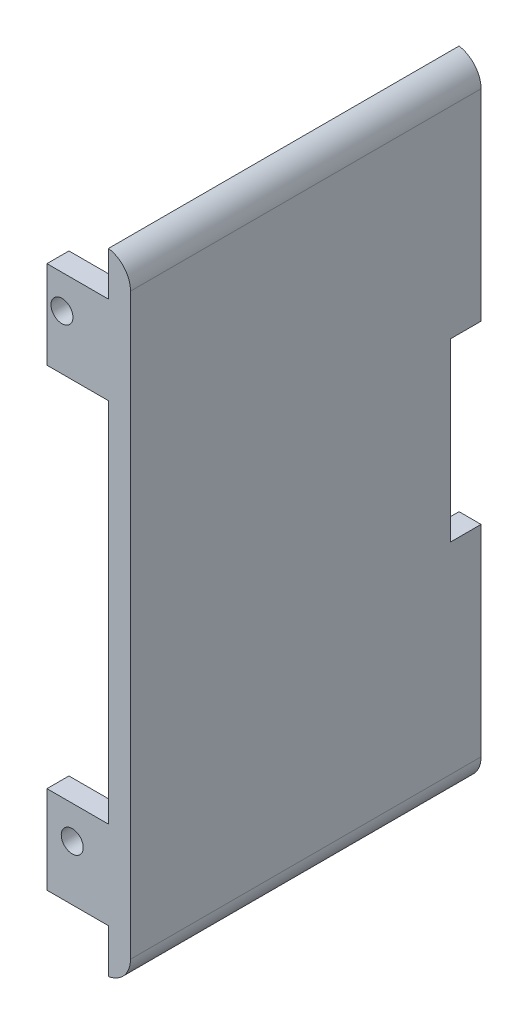
SolidWorks part; units mm, degrees
material "Aleación 1060"
ref_plane "Alzado" through (0, 0, 0) normal (0, 0, 1) x (1, 0, 0)
ref_plane "Planta" through (0, 0, 0) normal (0, 1, 0) x (1, 0, 0)
ref_plane "Vista lateral" through (0, 0, 0) normal (1, 0, 0) x (0, 0, -1)
sketch "Croquis2" plane through (0, 0, 0) normal (0, 0, 1) x (1, 0, 0)
  line L0 (64.1083, -69.3601) -> (64.1083, -63.6754) construction
  line L1 (-99.8917, -75.3601) -> (100.1083, -75.3601)
  line L2 (-99.8917, -75.3601) -> (-99.8917, 74.6399)
  line L3 (-99.8917, 74.6399) -> (100.1083, 74.6399)
  line L4 (100.1083, -75.3601) -> (100.1083, 74.6399)
  line L6 (100.1083, -69.3601) -> (-31.2492, -69.3601) construction
  line L7 (-32.0917, -69.3601) -> (-32.0917, -67.3601) construction
  line L8 (-62.0917, -69.3601) -> (-62.0917, -67.3601) construction
  line L11 (0.1083, -67.3601) -> (0.1083, -75.3601) construction
  line L15 (71.6083, -0.3601) -> (100.1083, -0.3601) construction
  line L34 (-99.8917, -0.3601) -> (-71.3917, -0.3601) construction
  line L35 (-62.0917, 70.6399) -> (64.1083, 70.6399)
  line L38 (-71.3917, -12.9024) -> (-71.3917, 12.1823)
  line L41 (-79.2417, -13.0101) -> (-71.3917, -12.9024)
  line L45 (92.1083, 45.4784) -> (92.1083, -46.1985)
  line L46 (89.1083, 45.8764) -> (89.1083, -46.5966)
  line L47 (84.1083, 12.2899) -> (84.1083, -13.0101)
  line L48 (84.1083, -13.0101) -> (79.4583, -13.0101)
  line L49 (71.6083, -13.0101) -> (71.6083, 12.2899)
  line L52 (79.4583, -13.0101) -> (71.6083, -13.0101)
  line L53 (84.1083, 12.2899) -> (79.4583, 12.2899)
  line L69 (-83.8917, -13.0101) -> (-79.2417, -13.0101)
  line L70 (-83.8917, 12.2899) -> (-83.8917, -13.0101)
  line L71 (-91.8917, 45.4784) -> (-91.8917, -46.1985)
  line L72 (-88.8917, 45.8764) -> (-88.8917, -46.5966)
  line L82 (79.4583, 12.2899) -> (71.6083, 12.2899)
  line L85 (-79.2417, 12.2899) -> (-71.3917, 12.1823)
  line L86 (-83.8917, 12.2899) -> (-79.2417, 12.2899)
  line L99 (-45.6601, 58.1834) -> (-14.3628, 58.1834)
  line L102 (64.1083, 66.6399) -> (-62.0917, 66.6399)
  line L103 (-62.0917, -71.3601) -> (64.1083, -71.3601)
  line L104 (64.1083, -67.3601) -> (-62.0917, -67.3601)
  line L118 (-45.6601, 58.1834) -> (-45.6601, 14.4146)
  line L119 (-45.6601, 14.4146) -> (-14.3628, 14.4146)
  line L120 (-14.3628, 58.1834) -> (-14.3628, 14.4146)
  line L121 (-45.6601, -4.9147) -> (-14.3628, -4.9147)
  line L122 (-45.6601, -4.9147) -> (-45.6601, -48.6834)
  line L123 (-45.6601, -48.6834) -> (-14.3628, -48.6834)
  line L124 (-14.3628, -4.9147) -> (-14.3628, -48.6834)
  line L125 (1.1959, 21.9686) -> (24.7698, 21.9686)
  line L126 (1.1959, 21.9686) -> (1.1959, -23.3553)
  line L127 (1.1959, -23.3553) -> (24.7698, -23.3553)
  line L128 (24.7698, 21.9686) -> (24.7698, -23.3553)
  circle A0 centre (89.1083, -66.5) radius 2
  arc A1 (64.1083, -71.3601) -> (64.1083, -67.3601) centre (64.1083, -69.3601) ccw
  arc A6 (-62.0917, -67.3601) -> (-62.0917, -71.3601) centre (-62.0917, -69.3601) ccw
  circle A8 centre (-88.8917, -66.5) radius 2
  arc A92 (89.1083, -46.5966) -> (92.1083, -46.1985) centre (90.6083, -46.3976) ccw
  arc A97 (-88.8917, -46.5966) -> (-91.8917, -46.1985) centre (-90.3917, -46.3976) cw
  arc A108 (-88.8917, 45.8764) -> (-91.8917, 45.4784) centre (-90.3917, 45.6774) ccw
  arc A109 (89.1083, 45.8764) -> (92.1083, 45.4784) centre (90.6083, 45.6774) cw
  circle A110 centre (89.1083, 65.7798) radius 2
  arc A113 (64.1083, 70.6399) -> (64.1083, 66.6399) centre (64.1083, 68.6399) cw
  arc A146 (-62.0917, 66.6399) -> (-62.0917, 70.6399) centre (-62.0917, 68.6399) cw
  circle A153 centre (-88.8917, 65.7798) radius 2
  circle A154 centre (-80.8654, -59.3601) radius 2.5
  circle A155 centre (81.1083, -59.3601) radius 2.5
  circle A156 centre (81.1083, 58.6399) radius 2.5
  circle A157 centre (-80.8654, 58.6399) radius 2.5
  point P0 (0, 0)
  point P78 (3.0535, -59.0858)
  point P80 (1.1959, -58.7698)
  point P84 (89.4782, -52.7527)
  point P89 (81.5012, -58.7833)
  point P95 (-80.8654, -59.3601)
  point P116 (-91.8917, -0.3601)
  point P120 (-5.0314, -61.027)
  point P121 (11.1384, -58.7698)
  point P128 (84.1083, -0.3601)
  point P135 (71.6083, -0.3601)
  point P139 (-71.3917, -0.3601)
  point P140 (-83.8917, -0.3601)
  point P143 (-88.8917, -0.3601)
  point P144 (0.0463, 58.5996)
  point P149 (89.1083, -0.3601)
  point P150 (92.1083, -0.3601)
  point P155 (81.5012, 58.0631)
  point P171 (49.6083, -0.3601)
  point P173 (46.6083, -0.3601)
  point P228 (1.1959, 58.2649)
  point P247 (7.6372, -0.3601)
  point P258 (-14.3628, -0.3601)
  point P290 (-80.8654, 58.38)
  dimension "D4" = 6
  dimension "D5" = 25
  dimension "D6" = 19.0263
  dimension "D7" = 16
  dimension "D9" = 16
  dimension "D19" = 26.8
  dimension "D32" = 8
  dimension "D22" = 3
  dimension "D8" = 19
  dimension "D1" = 200
  dimension "D2" = 150
  dimension "D10" = 11
  dimension "D11" = 11
  dimension "D35" = 12.65
  dimension "D36" = 5
  dimension "D42" = 4.65
  dimension "D43" = 12.5
extrude "Saliente-Extruir1" add sketch "Croquis2" along normal blind 2
fillet "Redondeo1" radius 10 4 edges at (-99.8917, 74.6399, 1) (-99.8917, -75.3601, 1) (100.1083, -75.3601, 1) (100.1083, 74.6399, 1)
sketch "Sketch1" plane through (0, 0, 2) normal (0, 0, 1) x (1, 0, 0)
  line L0 (-67.0718, 64.6399) -> (-67.0718, 60.6399)
  line L1 (-67.0718, 60.6399) -> (-8.8412, 60.6399)
  line L2 (-8.8412, 60.6399) -> (-8.8412, 3.6399)
  line L3 (-8.8412, 3.6399) -> (-67.0718, 3.6399)
  line L4 (-67.0718, 3.6399) -> (-67.0718, -0.3601)
  line L5 (-67.0718, -0.3601) -> (-8.8412, -0.3601)
  line L6 (-8.8412, -0.3601) -> (-8.8412, -53.3601)
  line L7 (-8.8412, -53.3601) -> (-67.0718, -53.3601)
  line L8 (-67.0718, -53.3601) -> (-67.0718, -57.5747)
  line L9 (-67.0718, -57.5747) -> (-5.0314, -57.5747)
  line L10 (-5.0314, -57.5747) -> (-5.0314, -40.9314)
  line L11 (-5.0314, -40.9314) -> (46.6083, -40.9314)
  line L12 (46.6083, -40.9314) -> (46.6083, -36.9314)
  line L13 (46.6083, -36.9314) -> (-5.0314, -36.9314)
  line L14 (-5.0314, -36.9314) -> (-5.0314, 30.0686)
  line L15 (-5.0314, 30.0686) -> (46.6083, 30.0686)
  line L16 (46.6083, 30.0686) -> (46.6083, 34.0686)
  line L17 (46.6083, 34.0686) -> (-5.0314, 34.0686)
  line L18 (-5.0314, 34.0686) -> (-5.0314, 64.6399)
  line L19 (-5.0314, 64.6399) -> (-67.0718, 64.6399)
extrude "Boss-Extrude1" add sketch "Sketch1" along normal blind 25
sketch "Sketch3" plane through (0, -57.5747, 0) normal (0, -1, 0) x (1, 0, 0)
  line L0 (-5.0314, 27) -> (-5.0314, 2) construction
  line L1 (-67.0718, 27) -> (-5.0314, 27)
  line L2 (-67.0718, 27) -> (-67.0718, 21.4692)
  line L3 (-67.0718, 21.4692) -> (-5.0314, 21.4692)
  line L4 (-5.0314, 27) -> (-5.0314, 21.4692)
extrude "Boss-Extrude2" add sketch "Sketch3" along normal blind 22
sketch "Sketch8" plane through (0, 64.6399, 0) normal (0, 1, 0) x (1, 0, 0)
  line L0 (-67.0718, -21.4692) -> (-5.0314, -21.4692)
  line L1 (-5.0314, -27) -> (-5.0314, -2) construction
  line L2 (-5.0314, -21.4692) -> (-5.0314, -27)
  line L3 (-5.0314, -27) -> (-67.0718, -27)
  line L4 (-67.0718, -27) -> (-67.0718, -21.4692)
extrude "Boss-Extrude6" add sketch "Sketch8" along normal blind 13
sketch "Sketch2" plane through (0, -75.3601, 0) normal (0, -1, 0) x (1, 0, 0)
  line L1 (-99.8917, 2) -> (100.1083, 2)
  line L2 (-99.8917, 2) -> (-99.8917, 80.1241)
  line L3 (-99.8917, 80.1241) -> (100.1083, 80.1241)
  line L4 (100.1083, 2) -> (100.1083, 80.1241)
  line L5 (-67.0718, 27) -> (-5.0314, 27)
  line L6 (-67.0718, 27) -> (-67.0718, 21.4692)
  line L7 (-67.0718, 21.4692) -> (-5.0314, 21.4692)
  line L8 (-5.0314, 27) -> (-5.0314, 21.4692)
extrude "Boss-Extrude3" add sketch "Sketch2" against normal blind 5
sketch "Sketch4" plane through (0, 64.6399, 0) normal (0, 1, 0) x (1, 0, 0)
  line L1 (-67.0718, -21.4692) -> (-5.0314, -21.4692)
  line L2 (-67.0718, -21.4692) -> (-67.0718, -27)
  line L3 (-67.0718, -27) -> (-5.0314, -27)
  line L4 (-5.0314, -21.4692) -> (-5.0314, -27)
extrude "Boss-Extrude4" add sketch "Sketch4" along normal blind 19
sketch "Sketch5" plane through (0, -75.3601, 0) normal (0, -1, 0) x (1, 0, 0)
  line L0 (0.1083, 80.1241) -> (0.1083, 0) construction
  line L1 (-84.2615, 2) -> (-76.8189, 2)
  line L2 (-84.2615, 2) -> (-84.2615, 4.9915)
  line L3 (-84.2615, 4.9915) -> (-76.8189, 4.9915)
  line L4 (-76.8189, 2) -> (-76.8189, 4.9915)
  line L5 (100.1083, 80.1241) -> (-99.8917, 80.1241) construction
  line L6 (-89.8917, 0) -> (90.1083, 0) construction
  line L7 (100.1083, 2) -> (100.1083, 80.1241) construction
  line L8 (84.478, 2) -> (84.478, 4.9915)
  line L9 (84.478, 2) -> (77.0354, 2)
  line L10 (77.0354, 2) -> (77.0354, 4.9915)
  line L11 (84.478, 4.9915) -> (77.0354, 4.9915)
  dimension "D1" = 100
extrude "Boss-Extrude5" add sketch "Sketch5" along normal blind 21
sketch "Sketch6" plane through (0, 0, 4.9915) normal (0, 0, 1) x (1, 0, 0)
  line L0 (0, 0) -> (0.1083, -75.3601) construction
  line L1 (100.1083, -75.3601) -> (-99.8917, -75.3601) construction
  circle A0 centre (-80.996, -59.2843) radius 2.5
  circle A1 centre (81.166, -59.0514) radius 2.5
extrude "Cut-Extrude1" cut sketch "Sketch6" against normal through all
fillet "Fillet1" radius 10 2 edges at (100.1083, -70.3601, 41.0621) (-99.8917, -70.3601, 41.0621)
sketch "Sketch10" plane through (-99.8917, 0, 0) normal (-1, 0, 0) x (0, 0, 1)
  line L1 (0, 71.4003) -> (-79.689, 71.4003)
  line L2 (0, 71.4003) -> (0, -71.9583)
  line L3 (0, -71.9583) -> (-79.689, -71.9583)
  line L4 (-79.689, 71.4003) -> (-79.689, -71.9583)
extrude "Boss-Extrude7" add sketch "Sketch10" along normal blind 5 separate body
sketch "Sketch11" plane through (-104.8917, 0, 0) normal (-1, 0, 0) x (0, 0, 1)
  line L0 (0, 64.6399) -> (0, -65.3601) construction
  line L1 (0, -61.9583) -> (-5, -61.9583)
  line L2 (0, -61.9583) -> (0, -41.9583)
  line L3 (0, -41.9583) -> (-5, -41.9583)
  line L4 (-5, -61.9583) -> (-5, -41.9583)
  line L5 (-79.689, -71.9583) -> (0, -71.9583) construction
  line L6 (0, -0.279) -> (-79.689, -0.279) construction
  line L7 (0, -71.9583) -> (0, 71.4003) construction
  line L8 (-79.689, 71.4003) -> (-79.689, -71.9583) construction
  line L9 (0, 61.4003) -> (-5, 61.4003)
  line L10 (0, 61.4003) -> (0, 41.4003)
  line L11 (0, 41.4003) -> (-5, 41.4003)
  line L12 (-5, 61.4003) -> (-5, 41.4003)
  dimension "D1" = 10
  dimension "D2" = 5
  dimension "D3" = 20
extrude "Boss-Extrude13" add sketch "Sketch11" along normal blind 14
sketch "Sketch12" plane through (0, 0, -5) normal (0, 0, -1) x (-1, 0, 0)
  line L0 (99.8917, -0.279) -> (71.3917, -0.279) construction
  line L1 (99.8917, -71.9583) -> (99.8917, 71.4003) construction
  line L2 (104.8917, 71.4003) -> (104.8917, -71.9583) construction
  line L3 (99.8917, -71.9583) -> (99.8917, 71.4003) construction
  circle A0 centre (94.3069, -54.336) radius 2.5
  circle A1 centre (94.3069, 53.7781) radius 2.5
  circle A3 centre (115.4766, 53.7781) radius 2.5
  circle A4 centre (113.141, -49.4453) radius 2.5
  dimension "D1" = 5
  dimension "D2" = 21.024
  dimension "D3" = 5.5849
extrude "Cut-Extrude2" cut sketch "Sketch12" against normal through all
fillet "Fillet2" radius 6 2 edges at (-99.8917, -71.9583, -39.8445) (-99.8917, 71.4003, -39.8445)
sketch "Sketch13" plane through (0, 0, 80.1241) normal (0, 0, 1) x (1, 0, 0)
  line L0 (-118.8917, 41.4003) -> (-104.8917, 41.4003) construction
  line L1 (-88.8917, 41.4003) -> (-87.8917, 41.4003)
  line L5 (-88.8917, -46.5966) -> (-88.8917, 45.8764) construction
  line L7 (-88.4783, -40.956) -> (-99.8917, -40.956)
  line L8 (-99.8917, 64.6399) -> (-99.8917, -65.3601) construction
  line L9 (-88.8917, 41.4003) -> (-99.8917, 41.4003)
  line L10 (-99.8917, 41.4003) -> (-99.8917, -40.956)
  line L11 (-99.8917, -61.923) -> (-99.8917, -102.1238)
  line L12 (-99.8917, -102.1238) -> (108.4876, -102.1238)
  line L13 (108.4876, -102.1238) -> (108.4876, 94.0101)
  line L14 (108.4876, 94.0101) -> (-99.8917, 94.0101)
  line L15 (-88.4783, -40.956) -> (-88.4783, -61.923)
  line L16 (-88.4783, -61.923) -> (-99.8917, -61.923)
  line L17 (-87.8917, 41.4003) -> (-87.8917, 63.5255)
  line L18 (-87.8917, 63.5255) -> (-99.8917, 63.5255)
  line L19 (-99.8917, 94.0101) -> (-99.8917, 63.5255)
extrude "Cut-Extrude3" cut sketch "Sketch13" against normal through all
sketch "Sketch14" plane through (0, 63.5255, 0) normal (0, 1, 0) x (1, 0, 0)
  line L0 (-87.8917, -2) -> (-99.8917, -2) construction
  line L1 (-99.8917, 0) -> (-87.8917, 0)
  line L2 (-99.8917, 0) -> (-99.8917, -2)
  line L3 (-99.8917, -2) -> (-87.8917, -2)
  line L4 (-87.8917, 0) -> (-87.8917, -2)
extrude "Cut-Extrude4" cut sketch "Sketch14" against normal through all
sketch "Sketch15" plane through (-104.8917, 0, 0) normal (-1, 0, 0) x (0, 0, 1)
  line L0 (0, -0.279) -> (-79.689, -0.279) construction
  line L1 (0, -41.9583) -> (0, 41.4003) construction
  line L2 (-79.689, 71.4003) -> (-79.689, -71.9583) construction
  line L4 (-79.689, 19.721) -> (-72.689, 19.721)
  line L5 (-79.689, 19.721) -> (-79.689, -20.279)
  line L6 (-79.689, -20.279) -> (-72.689, -20.279)
  line L7 (-72.689, 19.721) -> (-72.689, -20.279)
  dimension "D1" = 20
  dimension "D2" = 20
  dimension "D3" = 7
extrude "Cut-Extrude5" cut sketch "Sketch15" against normal blind 10
